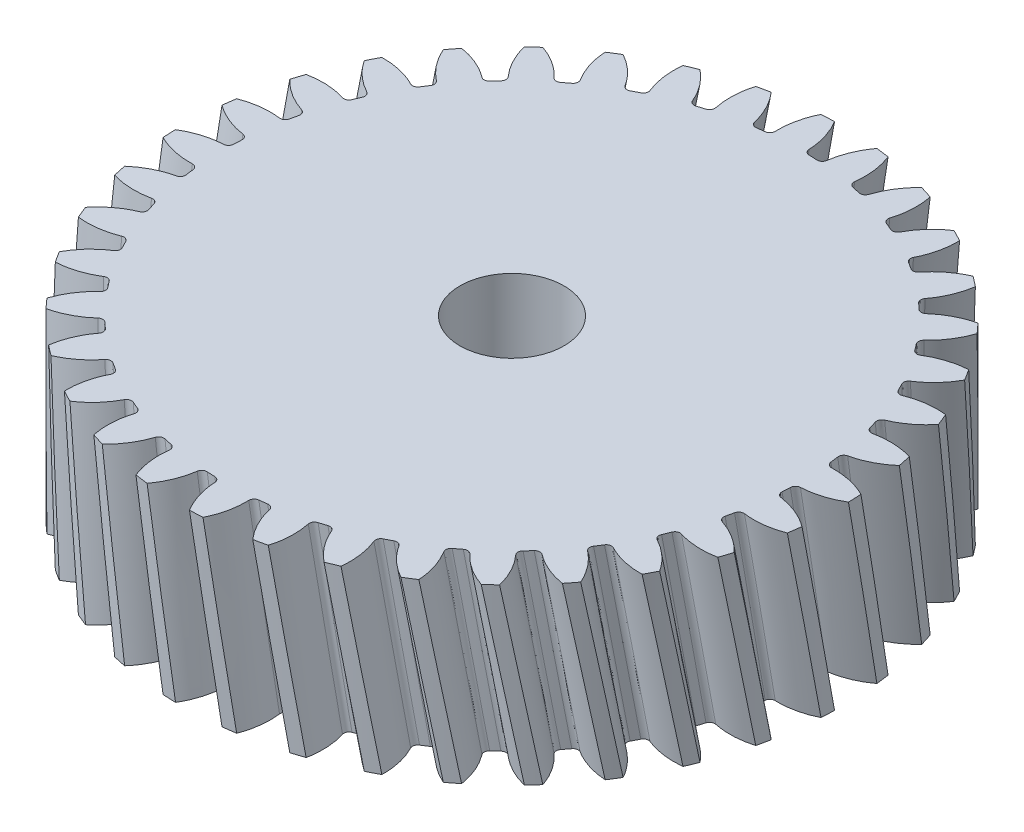
SolidWorks part; units mm, degrees
ref_plane "Front Plane" through (0, 0, 0) normal (0, 0, 1) x (1, 0, 0)
ref_plane "Top Plane" through (0, 0, 0) normal (0, 1, 0) x (1, 0, 0)
ref_plane "Right Plane" through (0, 0, 0) normal (1, 0, 0) x (0, 0, -1)
sketch "Sketch1" plane through (0, 0, 0) normal (0, 1, 0) x (1, 0, 0)
  circle A0 centre (0, 0) radius 18
  circle A1 centre (0, 0) radius 19
  circle A2 centre (0, 0) radius 16.6
  dimension "D1" = 36
  dimension "D2" = 38
  dimension "D3" = 2.4
extrude "Boss-Extrude1" add sketch "Sketch1" along normal mid plane 10 contours A1
sketch "Sketch2" plane through (0, 0, 0) normal (0, 1, 0) x (1, 0, 0)
  line L0 (0, 0) -> (0, 19) construction
  line L1 (-0.7851, 17.9829) -> (0.7851, 17.9829) construction
  line L2 (-0.5175, 16.5919) -> (0, 0) construction
  line L3 (-1.4989, 19.9438) -> (0, 15.8257) construction
  line L4 (0, 0) -> (1.656, 18.9277) construction
  line L5 (0.7851, 17.9829) -> (2.3495, 17.846) construction
  circle A0 centre (0, 0) radius 19 construction
  arc A1 (-2.1219, 19.8871) -> (-0.5175, 16.5919) centre (-4.99, 16.4524) cw
  arc A2 (2.1219, 19.8871) -> (0.5175, 16.5919) centre (4.99, 16.4524) ccw
  circle A3 centre (0, 0) radius 16.6 construction
  arc A4 (0.5175, 16.5919) -> (-0.5175, 16.5919) centre (0, 0) ccw
  circle A5 centre (0, 0) radius 18 construction
  circle A7 centre (0, 0) radius 20
  arc A8 (2.1219, 19.8871) -> (-2.1219, 19.8871) centre (0, 0) ccw
  circle A9 centre (0, 0) radius 19 construction
  dimension "D2" = 20
  dimension "D3" = 5
sketch "Sketch5" plane through (0, 0, 0) normal (0, 0, 1) x (1, 0, 0)
  line L0 (-0.8816, -5) -> (0.8816, 5)
  line L1 (-19, -5) -> (19, -5) construction
  line L2 (19, 5) -> (-19, 5) construction
  line L3 (0, -5) -> (0, 5) construction
  dimension "D1" = 10
curve "Curve1"
sketch "Sketch6" plane through (0, 5, 0) normal (0, 1, 0) x (0.9989, 0, 0.0464)
  line L0 (0, 0) -> (0, 19) construction
  line L1 (-0.7851, 17.9829) -> (0.7851, 17.9829) construction
  line L2 (-0.5175, 16.5919) -> (0, 0) construction
  line L3 (-1.4989, 19.9438) -> (0, 15.8257) construction
  line L4 (0, 0) -> (1.656, 18.9277) construction
  line L5 (0.7851, 17.9829) -> (2.3495, 17.846) construction
  arc A1 (-2.1219, 19.8871) -> (-0.5175, 16.5919) centre (-4.99, 16.4524) cw
  arc A2 (2.1219, 19.8871) -> (0.5175, 16.5919) centre (4.99, 16.4524) ccw
  arc A4 (0.5175, 16.5919) -> (-0.5175, 16.5919) centre (0, 0) ccw
  arc A8 (2.1219, 19.8871) -> (-2.1219, 19.8871) centre (0, 0) ccw
sketch "Sketch7" plane through (0, -5, 0) normal (0, 1, 0) x (0.9989, 0, -0.0464)
  line L0 (0, 0) -> (0, 19) construction
  line L1 (-0.7851, 17.9829) -> (0.7851, 17.9829) construction
  line L2 (-0.5175, 16.5919) -> (0, 0) construction
  line L3 (-1.4989, 19.9438) -> (0, 15.8257) construction
  line L4 (0, 0) -> (1.656, 18.9277) construction
  line L5 (0.7851, 17.9829) -> (2.3495, 17.846) construction
  arc A1 (-2.1219, 19.8871) -> (-0.5175, 16.5919) centre (-4.99, 16.4524) cw
  arc A2 (2.1219, 19.8871) -> (0.5175, 16.5919) centre (4.99, 16.4524) ccw
  arc A4 (0.5175, 16.5919) -> (-0.5175, 16.5919) centre (0, 0) ccw
  arc A8 (2.1219, 19.8871) -> (-2.1219, 19.8871) centre (0, 0) ccw
loft "Cut-Loft1" cut profiles "Sketch6", "Sketch2", "Sketch7" start constraint default end constraint default
fillet "Fillet2" radius 0.3 2 edges
pattern_circular "CirPattern3" count 36 over 360 about axis through (0, 5, 0) along (0, -1, 0) of "Cut-Loft1", "Fillet2"
sketch "Sketch8" plane through (0, 5, 0) normal (0, 1, 0) x (1, 0, 0)
  circle A0 centre (0, 0) radius 3
  dimension "D1" = 6
extrude "Cut-Extrude1" cut sketch "Sketch8" against normal through all
equation "\"module\"= 1"
equation "\"number of teeth\"= 36"
equation "\"D1@Sketch1\"=\"module\"*\"number of teeth\""
equation "\"D2@Sketch1\"=(\"number of teeth\"+2) * \"module\""
equation "\"D3@Sketch1\"=\"module\"*if( \"module\"=>1.25,2.25,2.4)"
equation "\"pressure angle\"= 20deg"
equation "\"D2@Sketch2\"=\"pressure angle\""
equation "\"D3@Sketch2\"=180 / \"number of teeth\""
equation "\"helix angle\"= 10deg"
equation "\"D1@Sketch5\"=\"helix angle\""
equation "\"D1@Fillet2\"=\"module\"*.3"
equation "\"D1@CirPattern3\"=\"number of teeth\""
